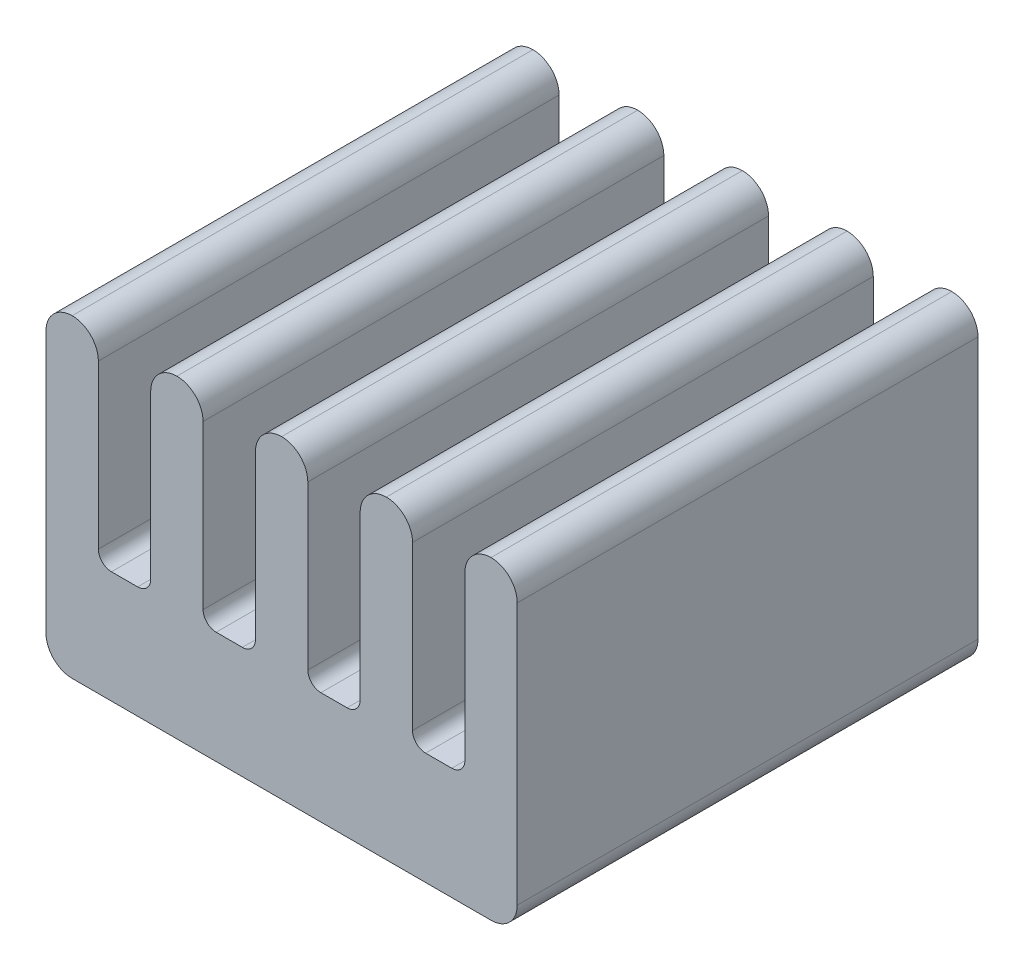
SolidWorks part; units mm, degrees
ref_plane "Front Plane" through (0, 0, 0) normal (0, 0, 1) x (1, 0, 0)
ref_plane "Top Plane" through (0, 0, 0) normal (0, 1, 0) x (1, 0, 0)
ref_plane "Right Plane" through (0, 0, 0) normal (1, 0, 0) x (0, 0, -1)
sketch "Sketch1" plane through (0, 0, 0) normal (0, 1, 0) x (1, 0, 0)
  line L1 (4.5, 4.4) -> (-4.5, 4.4)
  line L2 (4.5, 4.4) -> (4.5, -4.4)
  line L3 (4.5, -4.4) -> (-4.5, -4.4)
  line L4 (-4.5, 4.4) -> (-4.5, -4.4)
  line L5 (4.5, 4.4) -> (-4.5, -4.4) construction
  line L6 (4.5, -4.4) -> (-4.5, 4.4) construction
  circle A0 centre (0, 0) radius 2.5 construction
  point P0 (0, 0)
  dimension "D3" = 5
  dimension "D1" = 8.8
  dimension "D2" = 9
extrude "Boss-Extrude1" add sketch "Sketch1" along normal blind 6
sketch "Sketch2" plane through (0, 0, 4.4) normal (0, 0, 1) x (1, 0, 0)
  line L0 (-4.5, 6) -> (4.5, 6) construction
  line L1 (-3.5, 6) -> (-2.5, 6)
  line L2 (-3.5, 6) -> (-3.5, 2.14)
  line L3 (-3.5, 2.14) -> (-2.5, 2.14)
  line L4 (-2.5, 6) -> (-2.5, 2.14)
  line L5 (-3.5, 6) -> (-2.5, 2.14) construction
  line L6 (-3.5, 2.14) -> (-2.5, 6) construction
  line L7 (-4.5, 6) -> (-4.5, 0) construction
  point P0 (-3, 4.07)
  dimension "D1" = 3.86
  dimension "D2" = 1
  dimension "D3" = 1
extrude "Cut-Extrude1" cut sketch "Sketch2" against normal through all
pattern_linear "LPattern1" count 4 spacing 2 along (1, 0, 0) of "Cut-Extrude1"
fillet "Fillet1" radius 0.25 8 edges at (2.5, 2.14, 0) (3.5, 2.14, 0) (1.5, 2.14, 0) (0.5, 2.14, 0) (-0.5, 2.14, 0) (-1.5, 2.14, 0) (-2.5, 2.14, 0) (-3.5, 2.14, 0)
fillet "Fillet2" radius 0.5 12 edges at (-4.5, 6, 0) (-3.5, 6, 0) (-2.5, 6, 0) (-1.5, 6, 0) (-0.5, 6, 0) (0.5, 6, 0) (1.5, 6, 0) (2.5, 6, 0) (3.5, 6, 0) (4.5, 6, 0) (-4.5, 0, 0) (4.5, 0, 0)
